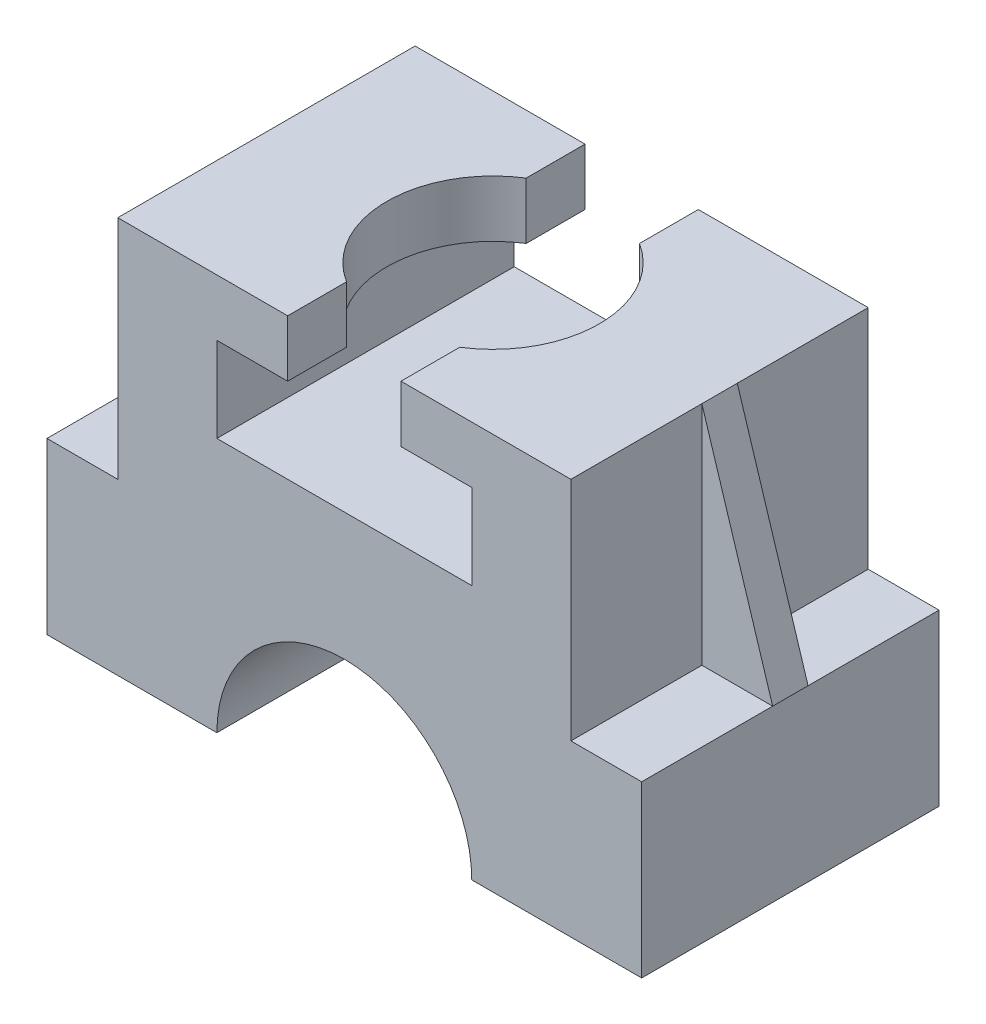
SolidWorks part; units mm, degrees
ref_plane "Front Plane" through (0, 0, 0) normal (0, 0, 1) x (1, 0, 0)
ref_plane "Top Plane" through (0, 0, 0) normal (0, 1, 0) x (1, 0, 0)
ref_plane "Right Plane" through (0, 0, 0) normal (1, 0, 0) x (0, 0, -1)
sketch "Sketch1" plane through (0, 0, 0) normal (0, 0, 1) x (1, 0, 0)
  line L0 (-105, 0) -> (105, 0)
  line L1 (105, 0) -> (105, 60)
  line L2 (105, 60) -> (80, 60)
  line L3 (80, 60) -> (80, 140)
  line L4 (80, 140) -> (-80, 140)
  line L5 (-80, 140) -> (-80, 60)
  line L6 (-80, 60) -> (-105, 60)
  line L7 (-105, 60) -> (-105, 0)
  line L8 (0, 0) -> (0, 198.7713) construction
  dimension "D1" = 210
  dimension "D2" = 60
  dimension "D3" = 140
  dimension "D4" = 160
extrude "Boss-Extrude1" add sketch "Sketch1" along normal blind 52.5 and the other way blind 52.5
sketch "Sketch2" plane through (0, 0, 52.5) normal (0, 0, 1) x (1, 0, 0)
  line L0 (-105, 0) -> (105, 0) construction
  line L1 (-45, 0) -> (45, 0)
  arc A0 (-45, 0) -> (45, 0) centre (0, 0) cw
  dimension "D1" = 45
extrude "Cut-Extrude1" cut sketch "Sketch2" against normal through all
sketch "Sketch3" plane through (0, 0, 52.5) normal (0, 0, 1) x (1, 0, 0)
  line L3 (-45, 120) -> (-45, 90)
  line L4 (-45, 90) -> (45, 90)
  line L5 (45, 90) -> (45, 120)
  line L9 (0, 0) -> (0, 152.2299) construction
  line L10 (-45, 120) -> (45, 120)
  line L11 (80, 140) -> (-80, 140) construction
  dimension "D1" = 90
  dimension "D2" = 20
  dimension "D3" = 30
extrude "Cut-Extrude2" cut sketch "Sketch3" against normal through all
sketch "Sketch5" plane through (0, 140, 0) normal (0, 1, 0) x (1, 0, 0)
  line L0 (-20, 52.5) -> (-20, 31.7214)
  line L1 (20, 52.5) -> (20, 31.7214)
  line L2 (0, 0) -> (0, 79.1682) construction
  line L3 (80, -52.5) -> (-80, -52.5) construction
  line L4 (80, 52.5) -> (-80, 52.5) construction
  line L5 (20, -52.5) -> (-20, -52.5)
  line L6 (20, 52.5) -> (-20, 52.5)
  line L7 (-20, -31.7214) -> (-20, -52.5)
  line L8 (20, -31.7214) -> (20, -52.5)
  arc A0 (20, -31.7214) -> (20, 31.7214) centre (0, 0) ccw
  arc A1 (-20, 31.7214) -> (-20, -31.7214) centre (0, 0) ccw
  point P15 (20, 31.7214)
  point P16 (20, 31.7214)
  point P17 (20, 31.7214)
  dimension "D1" = 75
  dimension "D2" = 40
extrude "Cut-Extrude3" cut sketch "Sketch5" against normal up to next
sketch "Sketch6" plane through (0, 0, 0) normal (0, 0, 1) x (1, 0, 0)
  line L0 (80, 140) -> (105, 60)
  line L1 (80, 60) -> (80, 140) construction
  line L2 (105, 60) -> (80, 60)
  line L3 (80, 60) -> (80, 140)
  point P4 (0, 0)
  dimension "D1" = 80
extrude "Boss-Extrude2" add sketch "Sketch6" along normal mid plane 12.5
mirror "Mirror1" about plane through (0, 0, 0) normal (1, 0, 0) of "Boss-Extrude2"
